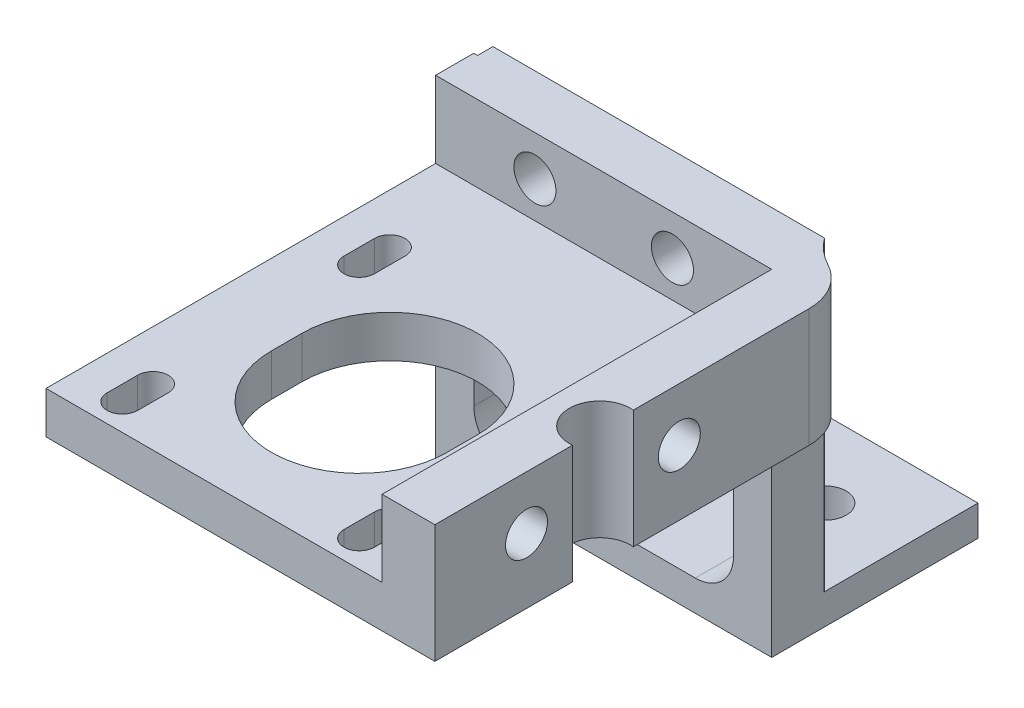
SolidWorks part; units mm, degrees
ref_plane "Front Plane" through (0, 0, 0) normal (0, 0, 1) x (1, 0, 0)
ref_plane "Top Plane" through (0, 0, 0) normal (0, 1, 0) x (1, 0, 0)
ref_plane "Right Plane" through (0, 0, 0) normal (1, 0, 0) x (0, 0, -1)
sketch "Sketch1" plane through (0, 0, 0) normal (1, 0, 0) x (0, 0, -1)
  line L0 (0, 0) -> (0, -62)
  line L1 (0, -62) -> (-5, -62)
  line L3 (-5, 0) -> (0, 0)
  line L4 (-56, 2.5) -> (-65, 2.5)
  line L5 (-65, 2.5) -> (-65, -15.5)
  arc A0 (-5, 0) -> (-56, 2.5) centre (-28.7567, 36.813) cw
  arc A1 (-5, -62) -> (-65, -15.5) centre (-67.324, -80.4584) ccw
  dimension "D3" = 51
  dimension "D5" = 43.813
  dimension "D8" = 65
  dimension "D1" = 5
  dimension "D2" = 62
  dimension "D4" = 2.5
  dimension "D6" = 9
  dimension "D7" = 18
  dimension "D9" = 5
extrude "Boss-Extrude1" add sketch "Sketch1" along normal blind 42 and the other way blind 42
sketch "Sketch2" plane through (0, 0, 0) normal (0, 0, -1) x (-1, 0, 0)
  line L0 (42, -62) -> (-42, -62) construction
  line L1 (-12, -54) -> (12, -54)
  line L2 (-17, -49) -> (-17, -25.5)
  line L3 (-12, -20.5) -> (12, -20.5)
  line L4 (17, -49) -> (17, -25.5)
  line L5 (42, -62) -> (42, 0) construction
  line L6 (42, 0) -> (-42, 0) construction
  line L7 (-42, -62) -> (-42, 0) construction
  line L8 (42, 2.5) -> (-42, 2.5) construction
  line L9 (-42, 0) -> (-27, 0)
  line L10 (-42, 0) -> (-42, 2.5)
  line L11 (-42, 2.5) -> (-27, 2.5)
  line L12 (-27, 0) -> (-27, 2.5)
  line L14 (42, 0) -> (27, 0)
  line L15 (42, 0) -> (42, 2.5)
  line L16 (42, 2.5) -> (27, 2.5)
  line L17 (27, 0) -> (27, 2.5)
  circle A0 centre (-36, -6) radius 2.75
  circle A1 centre (36, -6) radius 2.75
  circle A2 centre (36, -56) radius 2.75
  circle A3 centre (-36, -56) radius 2.75
  arc A4 (12, -20.5) -> (17, -25.5) centre (12, -25.5) cw
  arc A5 (12, -54) -> (17, -49) centre (12, -49) ccw
  arc A6 (-12, -54) -> (-17, -49) centre (-12, -49) cw
  arc A7 (-17, -25.5) -> (-12, -20.5) centre (-12, -25.5) cw
  arc A8 (-42, -8.3208) -> (-42, -53.6792) centre (-65.2788, -31) cw
  arc A9 (42, -8.3208) -> (42, -53.6792) centre (65.2788, -31) ccw
  line M7 (42, 0) -> (-42, 0)
  line M8 (-42, 0) -> (-42, -62)
  line M10 (42, -62) -> (42, 0)
  dimension "D1" = 5.5
  dimension "D2" = 5.5
  dimension "D3" = 5.5
  dimension "D4" = 5.5
  dimension "D9" = 5
  dimension "D18" = 8.3208
  dimension "D20" = 32.5
  dimension "D21" = 8.3208
  dimension "D23" = 32.5
  dimension "D5" = 33.5
  dimension "D6" = 34
  dimension "D7" = 8
  dimension "D8" = 25
  dimension "D10" = 6
  dimension "D11" = 6
  dimension "D12" = 6
  dimension "D13" = 6
  dimension "D14" = 6
  dimension "D15" = 6
  dimension "D16" = 6
  dimension "D17" = 6
  dimension "D19" = 8.3208
  dimension "D22" = 8.3208
  dimension "D24" = 15
  dimension "D25" = 15
extrude "Cut-Extrude1" cut sketch "Sketch2" against normal through all contours A0 | A8 M8 | A7 L2 A6 L1 A5 L4 A4 L3 | A3 | A2 | A1 | L17 L15 L16 M7 | L12 L11 L10 M7 | A9 M10 region at (0, -37.25, 0) region at (34.5, 1.25, 0) region at (-38.2626, -31, 0) region at (-34.5, 1.25, 0) region at (38.2626, -31, 0) region at (36, -6, 0) region at (-36, -6, 0) region at (-36, -56, 0) region at (36, -56, 0)
sketch "Sketch3" plane through (0, -62, 0) normal (0, -1, 0) x (-1, 0, 0)
  line L0 (42, -5) -> (27, -5)
  line L1 (42, -5) -> (-42, -5) construction
  line L2 (27, -5) -> (27, -65)
  line L3 (36.7131, -65) -> (-36.7131, -65) construction
  line L4 (0, -33) -> (0, -37) construction
  line L5 (-27, -65) -> (-27, -5)
  line L6 (-27, -5) -> (-42, -5)
  line L7 (-42, -5) -> (-42, -65)
  line L8 (-42, -65) -> (-27, -65)
  line L9 (42, -65) -> (42, -5)
  line L10 (42, -65) -> (27, -65)
  line L11 (11.5, -33) -> (11.5, -37)
  line L12 (-11.5, -33) -> (-11.5, -37)
  line L13 (15.5, -48.5) -> (15.5, -52.5) construction
  line L14 (17.5, -48.5) -> (17.5, -52.5)
  line L15 (13.5, -48.5) -> (13.5, -52.5)
  line L16 (15.5, -17.5) -> (15.5, -21.5) construction
  line L17 (17.5, -17.5) -> (17.5, -21.5)
  line L18 (13.5, -17.5) -> (13.5, -21.5)
  line L19 (42, 0) -> (-42, 0) construction
  line L20 (0, -65) -> (0, 0) construction
  line L21 (-15.5, -17.5) -> (-15.5, -21.5) construction
  line L22 (-17.5, -17.5) -> (-17.5, -21.5)
  line L23 (-13.5, -17.5) -> (-13.5, -21.5)
  line L24 (-15.5, -48.5) -> (-15.5, -52.5) construction
  line L25 (-17.5, -48.5) -> (-17.5, -52.5)
  line L26 (-13.5, -48.5) -> (-13.5, -52.5)
  circle A0 centre (0, -65) radius 4
  arc A1 (11.5, -33) -> (-11.5, -33) centre (0, -33) ccw
  arc A2 (-11.5, -37) -> (11.5, -37) centre (0, -37) ccw
  arc A3 (17.5, -48.5) -> (13.5, -48.5) centre (15.5, -48.5) ccw
  arc A4 (13.5, -52.5) -> (17.5, -52.5) centre (15.5, -52.5) ccw
  arc A5 (17.5, -17.5) -> (13.5, -17.5) centre (15.5, -17.5) ccw
  arc A6 (13.5, -21.5) -> (17.5, -21.5) centre (15.5, -21.5) ccw
  arc A7 (-17.5, -17.5) -> (-13.5, -17.5) centre (-15.5, -17.5) cw
  arc A8 (-13.5, -21.5) -> (-17.5, -21.5) centre (-15.5, -21.5) cw
  arc A9 (-17.5, -48.5) -> (-13.5, -48.5) centre (-15.5, -48.5) cw
  arc A10 (-13.5, -52.5) -> (-17.5, -52.5) centre (-15.5, -52.5) cw
  point P21 (0, -35)
  point P26 (15.5, -50.5)
  point P33 (15.5, -19.5)
  point P45 (-15.5, -19.5)
  point P52 (-15.5, -50.5)
  dimension "D3" = 8
  dimension "D4" = 11.5
  dimension "D9" = 2
  dimension "D10" = 2
  dimension "D1" = 15
  dimension "D2" = 15
  dimension "D5" = 4
  dimension "D6" = 28
  dimension "D7" = 4
  dimension "D8" = 4
  dimension "D11" = 12.5
  dimension "D12" = 11.5
  dimension "D13" = 17.5
extrude "Cut-Extrude2" cut sketch "Sketch3" against normal through all
sketch "Sketch4" plane through (0, 0, 65) normal (0, 0, 1) x (1, 0, 0)
  line L0 (-27, -62) -> (27, -62) construction
  line L1 (-22, -62) -> (22, -62)
  line L2 (-22, -62) -> (-22, -15.5)
  line L3 (-22, -15.5) -> (22, -15.5)
  line L4 (22, -62) -> (22, -15.5)
  line L5 (4, -15.5) -> (27, -15.5) construction
  line L6 (27, -62) -> (27, -15.5) construction
  line L7 (-27, -15.5) -> (-27, -62) construction
  dimension "D1" = 46.5
  dimension "D2" = 5
  dimension "D3" = 5
extrude "Cut-Extrude3" cut sketch "Sketch4" against normal blind 60
sketch "Sketch5" plane through (0, 0, 0) normal (0, 1, 0) x (1, 0, 0)
  line L0 (-27, -56) -> (27, -56) construction
  line L1 (-22, -56) -> (22, -56)
  line L2 (-22, -56) -> (-22, -5)
  line L3 (-22, -5) -> (22, -5)
  line L4 (22, -56) -> (22, -5)
  line L5 (-27, -5) -> (27, -5) construction
  line L6 (-27, -5) -> (-27, -56) construction
  line L7 (27, -56) -> (27, -5) construction
  dimension "D1" = 5
  dimension "D2" = 5
extrude "Cut-Extrude4" cut sketch "Sketch5" against normal blind 10 and the other way blind 10
sketch "Sketch6" plane through (0, 0, 65) normal (0, 0, 1) x (1, 0, 0)
  line L0 (-27, 2.5) -> (-4, 2.5) construction
  line L1 (4, 2.5) -> (27, 2.5) construction
  circle A0 centre (-10, -5.5) radius 2.75
  circle A1 centre (10, -5.5) radius 2.75
  dimension "D1" = 5.5
  dimension "D2" = 5.5
  dimension "D3" = 10
  dimension "D4" = 10
  dimension "D5" = 8
  dimension "D6" = 8
extrude "Cut-Extrude5" cut sketch "Sketch6" against normal blind 4.6
sketch "Sketch7" plane through (0, 0, 5) normal (0, 0, 1) x (1, 0, 0)
  line L1 (27, 0) -> (42, 0)
  line L2 (27, 0) -> (27, -62)
  line L3 (27, -62) -> (42, -62)
  line L4 (42, 0) -> (42, -62)
  line L5 (-27, -62) -> (-42, -62)
  line L6 (-27, -62) -> (-27, 0)
  line L7 (-27, 0) -> (-42, 0)
  line L8 (-42, -62) -> (-42, 0)
extrude "Cut-Extrude6" cut sketch "Sketch7" against normal blind 63
sketch "Sketch8" plane through (0, 0, 0) normal (0, 0, -1) x (-1, 0, 0)
  line L0 (27, 0) -> (27, -62) construction
  line L1 (-27, -62) -> (27, -62)
  line L2 (-27, -62) -> (-27, -40)
  line L3 (-27, -40) -> (27, -40)
  line L4 (27, -62) -> (27, -40)
  dimension "D1" = 22
extrude "Cut-Extrude7" cut sketch "Sketch8" against normal blind 63
sketch "Sketch9" plane through (0, -40, 0) normal (0, -1, 0) x (1, 0, 0)
  line L1 (-27, 5) -> (27, 5)
  line L2 (-27, 5) -> (-27, -22)
  line L3 (-27, -22) -> (27, -22)
  line L4 (27, 5) -> (27, -22)
  dimension "D1" = 54
  dimension "D2" = 27
extrude "Boss-Extrude2" add sketch "Sketch9" along normal blind 4
fillet "Fillet1" radius 5 2 edges at (17, -40, 2.5) (-17, -40, 2.5)
sketch "Sketch12" plane through (0, -40, 0) normal (0, -1, 0) x (1, 0, 0)
  line L1 (-27, 16.4505) -> (-22, 16.4505)
  line L2 (-27, 16.4505) -> (-27, 5)
  line L3 (-27, 5) -> (-22, 5)
  line L4 (-22, 16.4505) -> (-22, 5)
  line L5 (22, 16.4505) -> (27, 16.4505)
  line L6 (22, 16.4505) -> (22, 5)
  line L7 (22, 5) -> (27, 5)
  line L8 (27, 16.4505) -> (27, 5)
extrude "Boss-Extrude4" add sketch "Sketch12" along normal blind 4
sketch "Sketch13" plane through (27, 0, 0) normal (1, 0, 0) x (0, 0, -1)
  circle A0 centre (-67.324, -80.4584) radius 65
extrude "Cut-Extrude8" cut sketch "Sketch13" against normal blind 113
sketch "Sketch14" plane through (0, -44, 0) normal (0, -1, 0) x (1, 0, 0)
  line L0 (-27, -22) -> (27, -22) construction
  line L3 (-22, 5) -> (-22, 13.5116) construction
  line L5 (22, 13.5116) -> (22, 5) construction
  circle A0 centre (12, -12) radius 2.75
  circle A1 centre (-12, -12) radius 2.75
  dimension "D1" = 5.5
  dimension "D4" = 10
  dimension "D2" = 10
  dimension "D3" = 10
extrude "Cut-Extrude9" cut sketch "Sketch14" against normal blind 15
sketch "Sketch15" plane through (0, 0, 5) normal (0, 0, 1) x (1, 0, 0)
  line L0 (-22, 0) -> (22, 0) construction
  line L1 (27, -7) -> (27, 2.5) construction
  line L2 (-27, 2.5) -> (-27, -7) construction
  circle A0 centre (9, -5.25) radius 2.75
  circle A1 centre (-9, -5.25) radius 2.75
  dimension "D1" = 5.5
  dimension "D4" = 18
  dimension "D2" = 5.25
  dimension "D3" = 18
extrude "Cut-Extrude10" cut sketch "Sketch15" against normal blind 15
sketch "Sketch16" plane through (0, 0, 65) normal (0, 0, 1) x (1, 0, 0)
  line L1 (-27, 2.5) -> (-22, 2.5)
  line L2 (-27, 2.5) -> (-27, -44)
  line L3 (-27, -44) -> (-22, -44)
  line L4 (-22, 2.5) -> (-22, -44)
  line L5 (27, 2.5) -> (22, 2.5)
  line L6 (27, 2.5) -> (27, -44)
  line L7 (27, -44) -> (22, -44)
  line L8 (22, 2.5) -> (22, -44)
extrude "Cut-Extrude11" cut sketch "Sketch16" against normal blind 90
sketch "Sketch17" plane through (-22, 0, 0) normal (-1, 0, 0) x (0, 0, 1)
  line L0 (5, -15.5) -> (65, -15.5) construction
  line L1 (65, 2.5) -> (56, 2.5)
  line L2 (65, 2.5) -> (65, -15.5)
  line L3 (65, -15.5) -> (56, -15.5)
  line L4 (56, 2.5) -> (56, -15.5)
  dimension "D1" = 9
extrude "Cut-Extrude12" cut sketch "Sketch17" against normal blind 90
ref_plane "Plane1" [suppressed] through (0, 0, 0) normal (1, 0, 0) x (0, 0, -1)
sketch "Sketch23" plane through (22, 0, 0) normal (1, 0, 0) x (0, 0, -1)
  line L1 (-56, -15.5) -> (0, -15.5)
  line L2 (-56, -15.5) -> (-56, 0)
  line L3 (-56, 0) -> (0, 0)
  line L4 (0, -15.5) -> (0, 0)
extrude "Boss-Extrude10" add sketch "Sketch23" along normal blind 6.9
sketch "Sketch18" plane through (-22, 0, 0) normal (-1, 0, 0) x (0, 0, 1)
  line L1 (56, -15.5) -> (0, -15.5)
  line L2 (56, -15.5) -> (56, 0)
  line L3 (56, 0) -> (0, 0)
  line L4 (0, -15.5) -> (0, 0)
  circle A0 centre (24, -7.25) radius 2.75
  circle A1 centre (44, -7.25) radius 2.75
  dimension "D1" = 5.5
  dimension "D2" = 20
  dimension "D3" = 12
  dimension "D4" = 7.25
extrude "Boss-Extrude5" add sketch "Sketch18" along normal blind 6.5
sketch "Sketch19" plane through (0, -15.5, 0) normal (0, -1, 0) x (1, 0, 0)
  line L0 (-28.5, 0) -> (-28.5, 56) construction
  circle A0 centre (-28.5, 34) radius 4
  dimension "D2" = 8
  dimension "D1" = 22
extrude "Cut-Extrude13" cut sketch "Sketch19" against normal blind 36
fillet "Fillet2" radius 7 1 edges at (-28.5, -7.75, 0)
mirror "Mirror5" about plane through (0, 0, 0) normal (1, 0, 0) of "Cut-Extrude13"
fillet "Fillet5" radius 7 1 edges at (28.9, -7.75, 0)
sketch "Sketch24" plane through (28.9, 0, 0) normal (1, 0, 0) x (0, 0, -1)
  line L0 (-56, 0) -> (-56, -15.5) construction
  line L2 (-56, -15.5) -> (-37.9799, -15.5) construction
  circle A0 centre (-44, -7) radius 2.75
  circle A1 centre (-24, -7) radius 2.75
  dimension "D1" = 5.5
  dimension "D4" = 8.5
  dimension "D2" = 12
  dimension "D3" = 20
extrude "Cut-Extrude14" cut sketch "Sketch24" against normal blind 6.5
sketch "Sketch26" plane through (-28.5, 0, 0) normal (-1, 0, 0) x (0, 0, 1)
  line L1 (56, -15.5) -> (0, -15.5)
  line L2 (56, -15.5) -> (56, 0)
  line L3 (56, 0) -> (0, 0)
  line L4 (0, -15.5) -> (0, 0)
extrude "Cut-Extrude15" cut sketch "Sketch26" against normal blind 6.5
sketch "Sketch27" plane through (0, 0, 0) normal (0, 0, -1) x (-1, 0, 0)
  line L0 (-12, -20.5) -> (12, -20.5)
  line L1 (-21.9, -40) -> (22, -40)
  line L2 (-21.9, -40) -> (-21.9, 0)
  line L3 (-21.9, 0) -> (22, 0)
  line L4 (22, -40) -> (22, 0)
  line L5 (17, -25.5) -> (17, -35)
  line L6 (12, -40) -> (-12, -40)
  line L7 (-17, -25.5) -> (-17, -35)
  circle A0 centre (-9, -5.25) radius 2.75
  circle A1 centre (9, -5.25) radius 2.75
  arc A4 (-17, -35) -> (-12, -40) centre (-12, -35) ccw
  arc A5 (-12, -20.5) -> (-17, -25.5) centre (-12, -25.5) ccw
  arc A8 (17, -25.5) -> (12, -20.5) centre (12, -25.5) ccw
  arc A9 (12, -40) -> (17, -35) centre (12, -35) ccw
  line M1 (21.5, 0) -> (-21.9, 0)
  line M2 (-21.9, 0) -> (-21.9, -40)
  line M3 (-21.9, -40) -> (-12, -40)
  arc M4 (-12, -40) -> (-17, -35) centre (-12, -35) cw
  line M5 (-17, -35) -> (-17, -25.5)
  arc M6 (-17, -25.5) -> (-12, -20.5) centre (-12, -25.5) cw
  line M7 (-12, -20.5) -> (12, -20.5)
  arc M8 (12, -20.5) -> (17, -25.5) centre (12, -25.5) cw
  line M9 (17, -25.5) -> (17, -35)
  arc M10 (17, -35) -> (12, -40) centre (12, -35) cw
  line M11 (12, -40) -> (21.5, -40)
  line M12 (21.5, -40) -> (21.5, 0)
  circle M13 centre (9, -5.25) radius 2.75
  circle M14 centre (-9, -5.25) radius 2.75
extrude "Boss-Extrude11" add sketch "Sketch27" along normal blind 2 contours M12 M1 M2 M3 M4 M5 M6 M7 M8 M9 M10 M11 M13 M14 region at (0.3316, -14.3885, 0)
fillet "Fillet6" radius 10 1 edges at (21.9, -20, 0)
